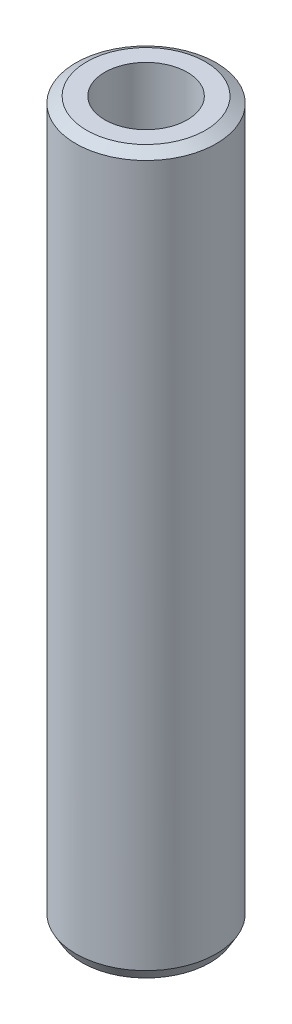
SolidWorks part; units mm, degrees
ref_plane "Front Plane" through (0, 0, 0) normal (0, 0, 1) x (1, 0, 0)
ref_plane "Top Plane" through (0, 0, 0) normal (0, 1, 0) x (1, 0, 0)
ref_plane "Right Plane" through (0, 0, 0) normal (1, 0, 0) x (0, 0, -1)
sketch "Sketch1" plane through (0, 0, 0) normal (0, 1, 0) x (1, 0, 0)
  circle A0 centre (0, 0) radius 40
  dimension "SHAFT_OD" = 80
extrude "Boss-Extrude1" add sketch "Sketch1" along normal blind 409.5889
sketch "Sketch2" plane through (0, 0, 0) normal (0, 1, 0) x (1, 0, 0)
  circle A0 centre (0, 0) radius 23.5126
  dimension "BORE_D" = 47.0253
extrude "Cut-Extrude1" cut sketch "Sketch2" along normal through all
chamfer "Chamfer1" distance 3.552 angle 60 2 edges at (0, 409.5889, 40) (0, 0, 40) first distance on face at (0, 409.5889, 40) first distance on face at (0, 0, 23.5126)
